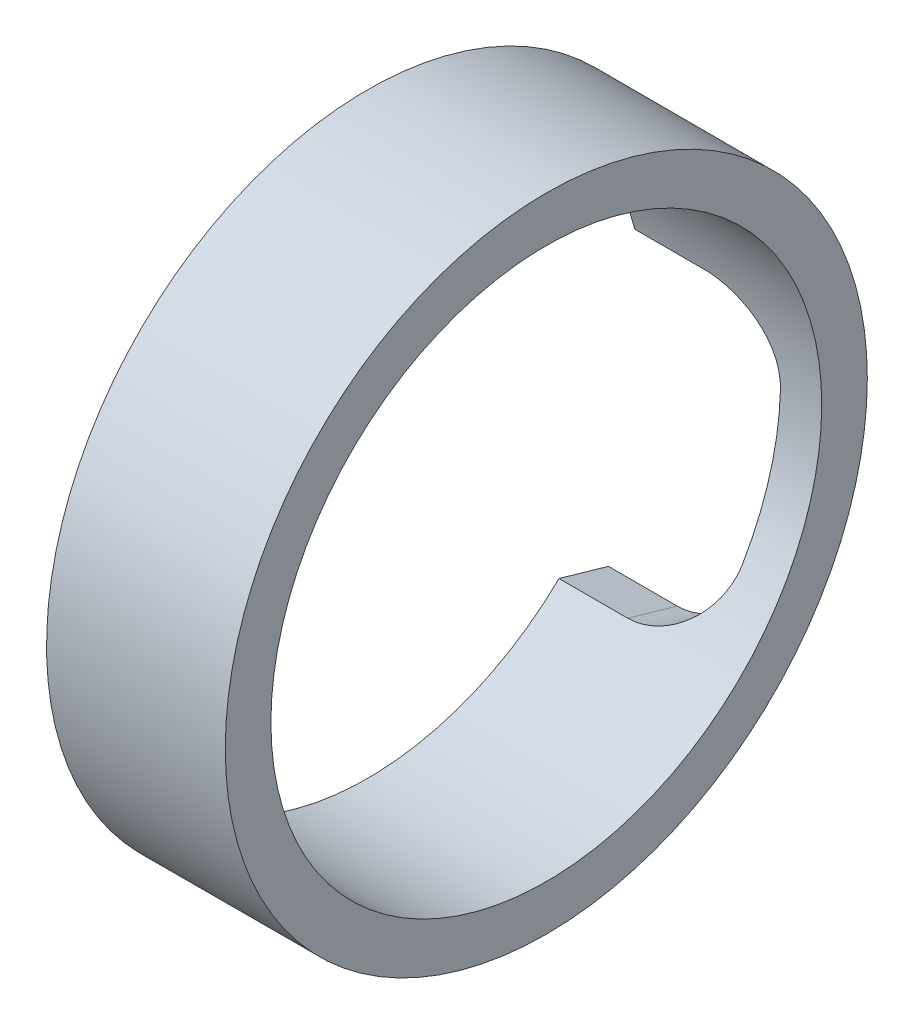
SolidWorks part; units mm, degrees
material "6061-T6 (SS)"
ref_plane "Front Plane" through (0, 0, 0) normal (0, 0, 1) x (1, 0, 0)
ref_plane "Top Plane" through (0, 0, 0) normal (0, 1, 0) x (1, 0, 0)
ref_plane "Right Plane" through (0, 0, 0) normal (1, 0, 0) x (0, 0, -1)
sketch "Sketch1" plane through (0, 0, 0) normal (0, 0, 1) x (1, 0, 0)
  line L1 (-39.3781, 8.89) -> (-34.4281, 8.89)
  line L2 (-39.3781, 8.89) -> (-39.3781, 7.627)
  line L3 (-39.3781, 7.627) -> (-34.4281, 7.627)
  line L4 (-34.4281, 8.89) -> (-34.4281, 7.627)
  line L7 (0, 0) -> (-47.1489, 0) construction
  line L8 (-39.3781, 10.9492) -> (-39.3781, 44.9952) construction
  line L9 (-34.4281, 15.2446) -> (-34.4281, -15.2446) construction
  dimension "D4" = 17.78
  dimension "D1" = 15.254
revolve "Revolve1" add sketch "Sketch1" angle 360 about L7
ref_plane "Plane1" through (0, -1.7235, -6.0108) normal (0, -0.2756, -0.9613) x (-1, 0, 0)
sketch "Sketch3" plane through (0, -1.7235, -6.0108) normal (0, -0.2756, -0.9613) x (-1, 0, 0)
  line L0 (39.3781, 3.81) -> (39.3781, -3.81)
  line L1 (39.3781, -7.627) -> (39.3781, 7.627) construction
  line L2 (39.3781, -3.81) -> (37.4731, -3.81)
  line L3 (35.5681, -1.905) -> (35.5681, 1.905)
  line L4 (37.4731, 3.81) -> (39.3781, 3.81)
  line L5 (39.3781, -8.89) -> (39.3781, 8.89) construction
  line L6 (39.3781, -8.89) -> (39.3781, 8.89) construction
  line L7 (35.5681, 0) -> (39.3781, 0) construction
  arc A2 (37.4731, -3.81) -> (35.5681, -1.905) centre (37.4731, -1.905) cw
  arc A3 (35.5681, 1.905) -> (37.4731, 3.81) centre (37.4731, 1.905) cw
  dimension "D1" = 7.62
  dimension "D2" = 3.81
extrude "Cut-Extrude1" cut sketch "Sketch3" along normal up to next
equation "\"D1@Sketch1\"=15mm+0.01in"
